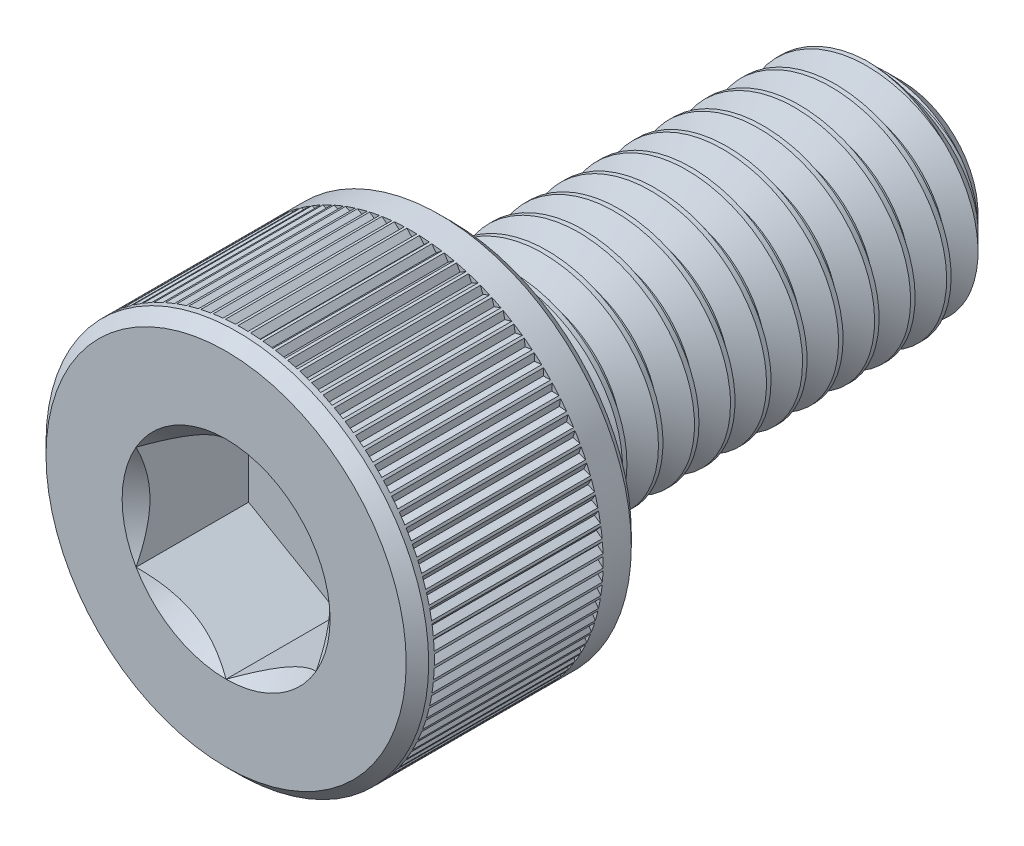
SolidWorks part; units mm, degrees
ref_plane "Front Plane" through (0, 0, 0) normal (0, 0, 1) x (1, 0, 0)
ref_plane "Top Plane" through (0, 0, 0) normal (0, 1, 0) x (1, 0, 0)
ref_plane "Right Plane" through (0, 0, 0) normal (1, 0, 0) x (0, 0, -1)
sketch "Sketch1" plane through (0, 0, 0) normal (1, 0, 0) x (0, 0, -1)
  line L0 (-7.5, 0) -> (7.5, 0) construction
  line L1 (7.5, 0) -> (7.5, 1.7) construction
  line L2 (7.5, 1.7) -> (6.7, 2.5) construction
  line L3 (6.7, 2.5) -> (-2.5, 2.5) construction
  line L5 (-2.5, 2.5) -> (-2.5, 4.25) construction
  line L6 (-2.5, 4.25) -> (-7.5, 4.25) construction
  line L7 (-7.5, 4.25) -> (-7.5, 0) construction
  line L8 (7.5, 1.7) -> (7.5, 2.5) construction
  line L9 (7.45, 2.5866) -> (7.85, 1.8938) construction
  line L10 (7.85, 1.8938) -> (8.25, 2.5866) construction
  line L11 (8.25, 2.5866) -> (7.45, 2.5866) construction
  line L12 (7.85, 2.5866) -> (7.85, 2.5) construction
  line L13 (7.85, 1.8938) -> (7.85, 1.9804) construction
  line L14 (7.8, 1.9804) -> (7.9, 1.9804) construction
  line L15 (7.5, 2.5) -> (8.2, 2.5) construction
  line L16 (7.475, 2.5433) -> (8.225, 2.5433) construction
  line L17 (7.5, 0) -> (7.5, -2.5) construction
  line L18 (-2.75, 4.25) -> (-2.5, 4) construction
  line L19 (-7.25, 4.25) -> (-7.5, 4) construction
  point P0 (-7.5, 2)
  point P3 (4.7, 2.5)
  point P4 (0, 0)
  point P22 (7.85, 1.9804)
  point P24 (-2.5, 2.5)
  point P25 (7.85, 2.5)
  point P28 (7.85, 2.5433)
  point P29 (4.7, -2.5)
  point P31 (-5, 4.25)
  point P37 (-3.375, 4.25)
  point P38 (-7.125, 4.25)
  point P41 (-5, 0)
  dimension "head height" = 5
  dimension "D1" = 45
  dimension "Head Diameter" = 8.5
  dimension "Thread Size" = 5
  dimension "drive size" = 4
  dimension "Thread Pitch" = 0.8
  dimension "D2" = 0.1
  dimension "D3" = 0.8
  dimension "D4" = 2.8
  dimension "D7" = 0.25
  dimension "D8" = 0.25
  dimension "D9" = 0.25
  dimension "D10" = 0.125
  dimension "D11" = 0.625
  dimension "length" = 10
  dimension "Drive Depth" = 2.5
sketch "Sketch2" plane through (0, 0, 0) normal (1, 0, 0) x (0, 0, -1)
  line L1 (-7.25, 4.25) -> (-2.75, 4.25)
  line L4 (6.7, 2.5) -> (7.5, 1.7)
  line L5 (7.5, 1.7) -> (7.5, 0)
  line L6 (-2.75, 4.25) -> (-2.5, 4) construction
  line L7 (7.5, 0) -> (-7.5, 0)
  line L8 (-7.25, 4.25) -> (-7.5, 4) construction
  line L9 (-2.75, 4.25) -> (-2.5, 4)
  line L10 (-7.25, 4.25) -> (-7.5, 4)
  line L11 (-7.5, 4) -> (-7.5, 0)
  line L12 (-2.5, 4) -> (-2.5, 2.5)
  line L13 (-2.5, 2.5) -> (6.7, 2.5)
revolve "Revolve1" add sketch "Sketch2" angle 360 about L7
sketch "Sketch3" plane through (0, 0, 7.5) normal (0, 0, 1) x (1, 0, 0)
  line L1 (0, 2.3094) -> (-2, 1.1547)
  line L2 (-2, 1.1547) -> (-2, -1.1547)
  line L3 (-2, -1.1547) -> (0, -2.3094)
  line L4 (0, -2.3094) -> (2, -1.1547)
  line L5 (2, -1.1547) -> (2, 1.1547)
  line L6 (2, 1.1547) -> (0, 2.3094)
  circle A0 centre (0, 0) radius 2 construction
  dimension "D1" = 4
extrude "Cut-Extrude1" cut sketch "Sketch3" against normal up to vertex (2.5 mm away) up to point (0, 0, 5)
sketch "Sketch4" plane through (0, 0, 7.5) normal (0, 0, 1) x (1, 0, 0)
  circle A0 centre (0, 0) radius 2.3094
extrude "Cut-Extrude2" cut sketch "Sketch4" against normal blind 0.5 draft 45
ref_plane "Plane1" through (0, 0, 2.5) normal (0, 0, 1) x (1, 0, 0)
split "Split1" bodies to split 106 resulting bodies 108 115 split by face at (-4, 0, 2.5)
sketch "Sketch6" plane through (0, 0, -7.5) normal (0, 0, -1) x (-1, 0, 0)
  circle A0 centre (0, 0) radius 2.5
curve "Helix/Spiral1" pitch 0.8 height 10.8 radius 2.5 centre (0, 0, -7.5) axis (0, 0, 1) start towards (0, 1, 0)
sketch "Sketch7" plane through (0, 0, 0) normal (1, 0, 0) x (0, 0, -1)
  line L0 (7.475, 2.5433) -> (8.225, 2.5433)
  line L1 (8.225, 2.5433) -> (7.9, 1.9804)
  line L2 (7.9, 1.9804) -> (7.8, 1.9804)
  line L3 (7.8, 1.9804) -> (7.475, 2.5433)
sweep "Cut-Sweep1" cut profiles "Sketch7" path "Helix/Spiral1" align with end faces yes
sketch "Sketch8" plane through (0, 0, 2.5) normal (0, 0, -1) x (-1, 0, 0)
  circle A0 centre (0, 0) radius 2.5
extrude "Boss-Extrude1" add sketch "Sketch8" along normal through all draft 45
ref_plane "Plane2" through (0, 0, 5) normal (0, 0, 1) x (1, 0, 0)
sketch "Sketch9" plane through (0, 0, 5) normal (0, 0, 1) x (1, 0, 0)
  line L0 (0, 4.1331) -> (0.1113, 4.2485)
  line L1 (0, 4.1331) -> (-0.1113, 4.2485)
  line L2 (0, 4.25) -> (0, 0) construction
  line L3 (-0.1113, 4.2485) -> (0, 0) construction
  line L4 (0, 0) -> (0.1113, 4.2485) construction
  arc A0 (0.1113, 4.2485) -> (-0.1113, 4.2485) centre (0, 0) ccw
  circle A1 centre (0, 0) radius 4.1331 construction
  dimension "D1" = 8.5
  dimension "D2" = 8.2662
  dimension "D3" = 3
extrude "Cut-Extrude4" cut sketch "Sketch9" against normal up to vertex (1.625 mm away) and the other way up to vertex (2.125 mm away) up to point (0, 4.25, 3.375) other way up to point (0, 4.25, 7.125)
pattern_circular "CirPattern2" count 96 over 360 about axis through (0, 0, 7.5) along (0, 0, -1) of "Cut-Extrude4"
equation "\"D2@Sketch1\" = \"Thread Pitch@Sketch1\" / 8"
equation "\"D3@Sketch1\" = \"Thread Pitch@Sketch1\""
equation "\"D3@Helix/Spiral1\" = \"length@Sketch1\" + \"Thread Pitch@Sketch1\""
equation "\"D4@Helix/Spiral1\" = \"Thread Pitch@Sketch1\""
equation "\"D4@Sketch1\" = \"Thread Pitch@Sketch1\" * 3.5"
equation "\"D7@Sketch1\"=\"head height@Sketch1\"*.05"
equation "\"D8@Sketch1\"=\"D7@Sketch1\""
equation "\"D9@Sketch1\"=\"D7@Sketch1\""
equation "\"D10@Sketch1\"=\"D7@Sketch1\"/2"
equation "\"D11@Sketch1\"=\"D10@Sketch1\"*5"
equation "\"D1@CirPattern2\"=( 360 / \"D3@Sketch9\" )*0.8"
equation "\"D1@Sketch3\" = \"drive size@Sketch1\""
equation "\"D2@Sketch9\"=\"Head Diameter@Sketch1\" * 0.9725"
